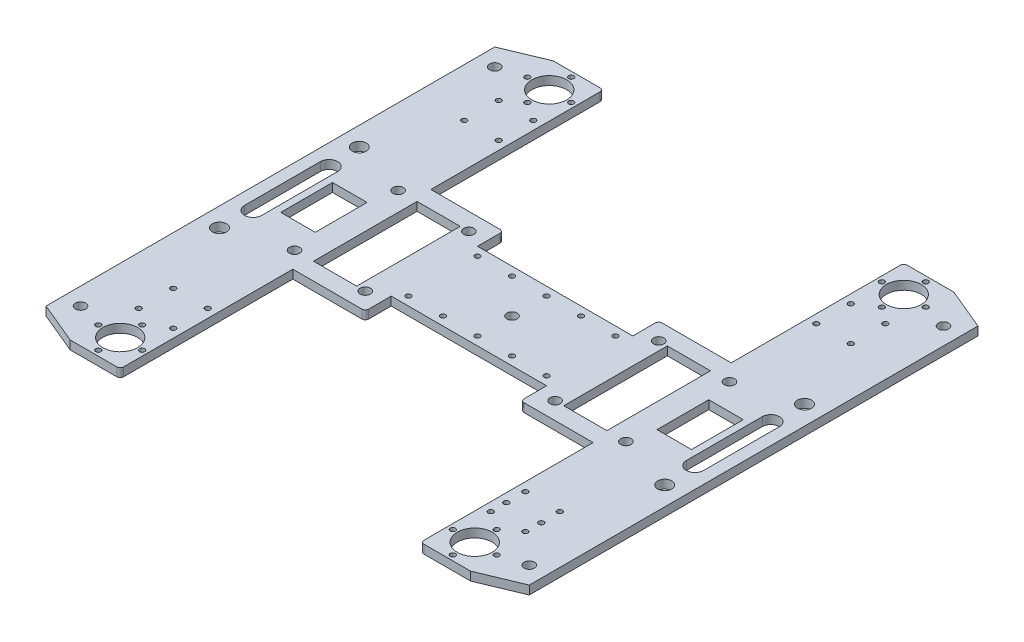
SolidWorks part; units mm, degrees
ref_plane "Plan de face" through (0, 0, 0) normal (0, 0, 1) x (1, 0, 0)
ref_plane "Plan de dessus" through (0, 0, 0) normal (0, 1, 0) x (1, 0, 0)
ref_plane "Plan de droite" through (0, 0, 0) normal (1, 0, 0) x (0, 0, -1)
sketch "Esquisse2" plane through (0, 0, 0) normal (0, 1, 0) x (1, 0, 0)
  line L0 (-140, 130) -> (-140, -130)
  line L1 (-140, 130) -> (-116, 140)
  line L2 (-116, 140) -> (-87, 140)
  line L3 (-140, -130) -> (-116, -140)
  line L4 (-116, -140) -> (-87, -140)
  line L5 (-87, 140) -> (-87, 40)
  line L6 (-87, 40) -> (-45, 40)
  line L7 (-45, 40) -> (-45, 25)
  line L8 (-45, 25) -> (45, 25)
  line L9 (0, 25) -> (0, -25) construction
  line L10 (45, -25) -> (-45, -25)
  line L11 (-45, -25) -> (-45, -40)
  line L12 (-45, -40) -> (-87, -40)
  line L13 (-87, -40) -> (-87, -140)
  line L14 (-128, 22) -> (-128, -22) construction
  line L15 (-85, 30) -> (-60, 30)
  line L16 (-85, 30) -> (-85, -30)
  line L17 (-85, -30) -> (-60, -30)
  line L18 (-60, 30) -> (-60, -30)
  line L19 (-123, 22) -> (-123, -22)
  line L20 (-133, 22) -> (-133, -22)
  line L21 (-119, 15) -> (-99, 15)
  line L22 (-119, 15) -> (-119, -15)
  line L23 (-119, -15) -> (-99, -15)
  line L24 (-99, 15) -> (-99, -15)
  line L25 (99, 15) -> (99, -15)
  line L26 (119, -15) -> (99, -15)
  line L27 (119, 15) -> (119, -15)
  line L28 (119, 15) -> (99, 15)
  line L29 (60, 30) -> (60, -30)
  line L30 (85, -30) -> (60, -30)
  line L31 (85, 30) -> (85, -30)
  line L32 (85, 30) -> (60, 30)
  line L33 (87, -40) -> (87, -140)
  line L34 (45, -40) -> (87, -40)
  line L35 (45, -25) -> (45, -40)
  line L36 (45, 40) -> (45, 25)
  line L37 (87, 40) -> (45, 40)
  line L38 (87, 140) -> (87, 40)
  line L39 (116, -140) -> (87, -140)
  line L40 (140, -130) -> (116, -140)
  line L41 (116, 140) -> (87, 140)
  line L42 (140, 130) -> (116, 140)
  line L43 (140, 130) -> (140, -130)
  line L44 (128, 22) -> (128, -22) construction
  line L45 (123, 22) -> (123, -22)
  line L46 (133, 22) -> (133, -22)
  circle A0 centre (-96, 30) radius 3
  circle A1 centre (-96, -30) radius 3
  circle A2 centre (-55, -30) radius 3
  circle A3 centre (-55, 30) radius 3
  arc A4 (-123, 22) -> (-133, 22) centre (-128, 22) ccw
  arc A5 (-133, -22) -> (-123, -22) centre (-128, -22) ccw
  circle A6 centre (-130, 120) radius 3
  circle A7 centre (-130, -120) radius 3
  circle A8 centre (-102.7, 124.3) radius 10.1
  circle A9 centre (-90, 124.3) radius 1.5
  circle A10 centre (-102.7, 137) radius 1.5
  circle A11 centre (-115.4, 124.3) radius 1.5
  circle A12 centre (-102.7, 111.6) radius 1.5
  circle A13 centre (-102.7, -124.3) radius 10.1
  circle A14 centre (-90, -124.3) radius 1.5
  circle A15 centre (-102.7, -111.6) radius 1.5
  circle A16 centre (-115.4, -124.3) radius 1.5
  circle A17 centre (-102.7, -137) radius 1.5
  circle A18 centre (102.7, -137) radius 1.5
  circle A19 centre (115.4, -124.3) radius 1.5
  circle A20 centre (102.7, -111.6) radius 1.5
  circle A21 centre (90, -124.3) radius 1.5
  circle A22 centre (102.7, -124.3) radius 10.1
  circle A23 centre (102.7, 111.6) radius 1.5
  circle A24 centre (115.4, 124.3) radius 1.5
  circle A25 centre (102.7, 137) radius 1.5
  circle A26 centre (90, 124.3) radius 1.5
  circle A27 centre (102.7, 124.3) radius 10.1
  circle A28 centre (130, -120) radius 3
  circle A29 centre (130, 120) radius 3
  circle A30 centre (55, 30) radius 3
  circle A31 centre (55, -30) radius 3
  circle A32 centre (96, -30) radius 3
  circle A33 centre (96, 30) radius 3
  arc A34 (123, 22) -> (133, 22) centre (128, 22) cw
  arc A35 (133, -22) -> (123, -22) centre (128, -22) cw
  circle A36 centre (-129, 40.5) radius 4.1
  circle A37 centre (-129, -40.5) radius 4.1
  circle A38 centre (129, -40.5) radius 4.1
  circle A39 centre (129, 40.5) radius 4.1
  circle A40 centre (0, 0) radius 3
  point P28 (-128, 0)
  point P116 (128, 0)
  dimension "D16" = 6
  dimension "D19" = 5
  dimension "D23" = 6
  dimension "D33" = 20.2
  dimension "D34" = 3
  dimension "D41" = 20.2
  dimension "D42" = 3
  dimension "D48" = 8.2
  dimension "D51" = 6
  dimension "D1" = 260
  dimension "D2" = 24
  dimension "D3" = 10
  dimension "D4" = 10
  dimension "D5" = 24
  dimension "D6" = 140
  dimension "D7" = 50
  dimension "D8" = 80
  dimension "D9" = 42
  dimension "D10" = 100
  dimension "D11" = 26
  dimension "D12" = 25
  dimension "D13" = 60
  dimension "D14" = 55
  dimension "D15" = 10
  dimension "D17" = 11
  dimension "D18" = 5
  dimension "D20" = 44
  dimension "D21" = 43
  dimension "D22" = 10
  dimension "D24" = 29
  dimension "D25" = 29
  dimension "D26" = 20
  dimension "D27" = 30
  dimension "D28" = 4
  dimension "D29" = 12.7
  dimension "D30" = 12.7
  dimension "D31" = 12.7
  dimension "D32" = 12.7
  dimension "D35" = 3
  dimension "D36" = 3
  dimension "D37" = 12.7
  dimension "D38" = 12.7
  dimension "D39" = 12.7
  dimension "D40" = 12.7
  dimension "D43" = 3
  dimension "D44" = 15
  dimension "D45" = 10
  dimension "D46" = 10
  dimension "D47" = 11
  dimension "D49" = 40.5
  dimension "D50" = 40.5
extrude "Boss.-Extru.1" add sketch "Esquisse2" along normal blind 5
fillet "Congé2" radius 2 8 edges at (-45, 2.5, -40) (45, 2.5, -40) (45, 2.5, 40) (-45, 2.5, 40) (87, 2.5, 140) (-87, 2.5, 140) (87, 2.5, -140) (-87, 2.5, -140)
hole_wizard "Diamètre du perçage Ø3.0 (3)1" positions "Esquisse4" profile "Esquisse3" hole size "Ø3.0" standard "Iso" end condition through all
sketch "Esquisse4" plane through (0, 5, 0) normal (0, 1, 0) x (1, 0, 0)
  line L0 (-87, 40) -> (-87, 138) construction
  line L1 (87, 138) -> (87, 40) construction
  circle A0 centre (-102.7, 124.3) radius 10.1 construction
  circle A1 centre (-102.7, -124.3) radius 10.1 construction
  point P0 (-92, 104.3)
  point P2 (-92, 84.3)
  point P4 (-20, 20)
  point P6 (0, 20)
  point P8 (20, 20)
  point P10 (20, -20)
  point P12 (0, -20)
  point P14 (-20, -20)
  point P16 (-92, -104.3)
  point P18 (-92, -84.3)
  point P20 (92, -104.3)
  point P22 (92, -84.3)
  point P24 (92, 104.3)
  point P26 (92, 84.3)
  point P35 (112, 104.3)
  point P37 (112, 84.3)
  point P39 (-112, 104.3)
  point P41 (-112, 84.3)
  point P43 (-112, -84.3)
  point P45 (-112, -104.3)
  point P47 (112, -104.3)
  point P49 (112, -84.3)
  point P51 (40, -20)
  point P53 (40, 20)
  point P55 (-40, 20)
  point P57 (-40, -20)
  dimension "D2" = 20
  dimension "D3" = 20
  dimension "D4" = 20
  dimension "D5" = 20
  dimension "D6" = 20
  dimension "D7" = 20
  dimension "D8" = 20
  dimension "D9" = 20
  dimension "D10" = 20
  dimension "D11" = 5
  dimension "D12" = 5
  dimension "D13" = 20
  dimension "D14" = 20
  dimension "D15" = 20
sketch "Esquisse3" plane through (-92, 5, -104.3) normal (1, 0, 0) x (0, 0, 1)
  line L0 (0, 0) -> (0, 5)
  line L1 (0, 5) -> (1.5, 5)
  line L2 (1.5, 5) -> (1.5, 0)
  line L5 (1.5, 0) -> (0, 0)
  line L11 (0, -6.35) -> (0, 107.95) construction
  dimension "Diamètre du perçage jusqu'au prochain" = 3
  dimension "Profondeur du perçage jusqu'au prochain" = 5
sketch "Esquisse5" plane through (0, 0, 0) normal (0, -1, 0) x (-1, 0, 0)
  circle A0 centre (136.241, 98.3487) radius 1.5
  circle A1 centre (136.241, 67.3487) radius 1.5
  circle A2 centre (105.934, 65.9402) radius 1.5
  circle A3 centre (105.241, 96.9402) radius 1.5
  dimension "D1" = 3
  dimension "D2" = 3
  dimension "D3" = 3
  dimension "D4" = 3
  dimension "D5" = 31
  dimension "D6" = 31
sketch "Esquisse6" plane through (0, 0, 0) normal (0, -1, 0) x (1, 0, 0)
  circle A0 centre (112.2187, 95.2736) radius 1.4959
  circle A1 centre (91.9957, 95.2736) radius 1.5101
  point P4 (112.2187, 95.2736)
  point P5 (91.9957, 95.2736)
extrude "Enlèv. mat.-Extru.1" cut sketch "Esquisse6" against normal blind 10
